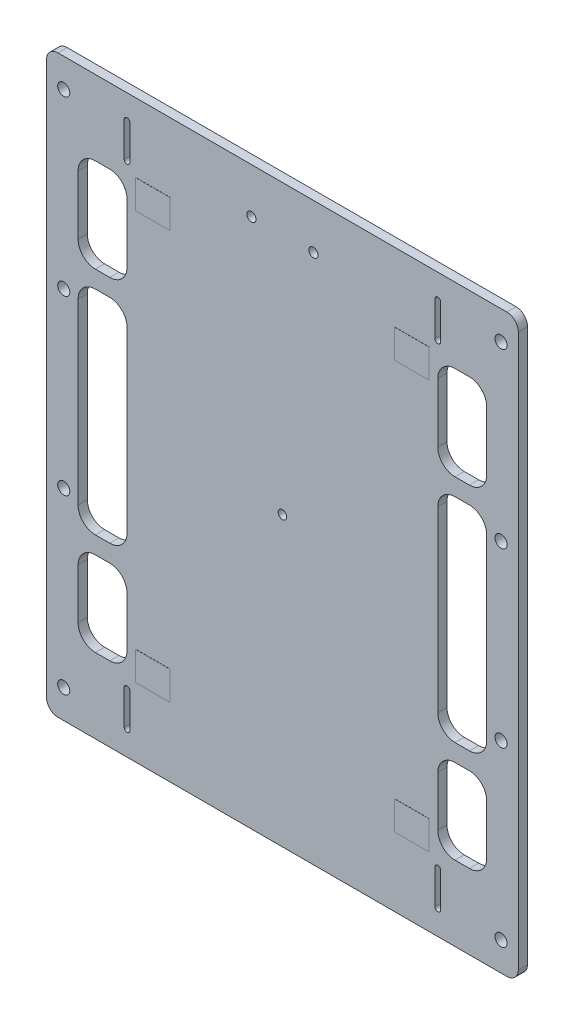
SolidWorks part; units mm, degrees
material "Oshpark board"
ref_plane "Front Plane" through (0, 0, 0) normal (0, 0, 1) x (1, 0, 0)
ref_plane "Top Plane" through (0, 0, 0) normal (0, 1, 0) x (1, 0, 0)
ref_plane "Right Plane" through (0, 0, 0) normal (1, 0, 0) x (0, 0, -1)
sketch "Sketch1" plane through (0, 0, 0) normal (0, 0, 1) x (1, 0, 0)
  line L1 (-39, -50) -> (39, -50)
  line L2 (-41, -48) -> (-41, 48)
  line L3 (-39, 50) -> (39, 50)
  line L4 (41, -48) -> (41, 48)
  line L5 (-41, -50) -> (41, 50) construction
  line L6 (-41, 50) -> (41, -50) construction
  arc A0 (-39, -50) -> (-41, -48) centre (-39, -48) cw
  arc A1 (39, -50) -> (41, -48) centre (39, -48) ccw
  arc A2 (39, 50) -> (41, 48) centre (39, 48) cw
  arc A3 (-41, 48) -> (-39, 50) centre (-39, 48) cw
  point P0 (0, 0)
  dimension "D3" = 2
  dimension "D1" = 100
  dimension "D2" = 82
extrude "boardOutline" add sketch "Sketch1" along normal blind 1.6
sketch "Sketch2" plane through (0, 0, 1.6) normal (0, 0, 1) x (1, 0, 0)
  line L0 (39, 50) -> (-39, 50) construction
  line L1 (-41, 48) -> (-41, -48) construction
  line L3 (-37.5, 44.2) -> (-37.5, 4.2) construction
  circle A0 centre (0, 0) radius 0.75
  circle A1 centre (-37.5, 44.2) radius 1.05 construction
  circle A2 centre (37.5, 44.2) radius 1.05 construction
  circle A3 centre (37.5, 4.2) radius 1.05 construction
  circle A4 centre (37.5, -35.8) radius 1.05 construction
  circle A5 centre (-37.5, 4.2) radius 1.05 construction
  circle A6 centre (-37.5, -35.8) radius 1.05 construction
  circle A7 centre (-5.38, 42.15) radius 0.8
  circle A8 centre (5.39, 42.15) radius 0.8
  dimension "D1" = 1.5
  dimension "D2" = 2.1
  dimension "D9" = 10.77
  dimension "D7" = 1.6
  dimension "D11" = 7.85
  dimension "D12" = 35.62
  dimension "D3" = 5.8
  dimension "D4" = 3.5
  dimension "D8" = 40
  dimension "D10" = 37.5
  dimension "D5" = 2
  dimension "D6" = 3
extrude "componentHoles" cut sketch "Sketch2" against normal through all
sketch "Sketch4" plane through (0, 0, 1.6) normal (0, 0, 1) x (1, 0, 0)
  line L0 (-27, 39.75) -> (-27, 45.75) construction
  line L1 (-27.5, 39.75) -> (-27.5, 45.75)
  line L2 (-26.5, 39.75) -> (-26.5, 45.75)
  line L3 (39, 50) -> (-39, 50) construction
  line L4 (-41, 48) -> (-41, -48) construction
  line L5 (27, 39.75) -> (27, 45.75) construction
  line L6 (26.5, 39.75) -> (26.5, 45.75)
  line L7 (27.5, 39.75) -> (27.5, 45.75)
  line L8 (27, -45.75) -> (27, -39.75) construction
  line L9 (26.5, -45.75) -> (26.5, -39.75)
  line L10 (27.5, -45.75) -> (27.5, -39.75)
  line L11 (-27, -45.75) -> (-27, -39.75) construction
  line L12 (-27.5, -45.75) -> (-27.5, -39.75)
  line L13 (-26.5, -45.75) -> (-26.5, -39.75)
  line L14 (-27, 39.75) -> (27, 39.75) construction
  line L15 (-39, -50) -> (39, -50) construction
  arc A0 (-27.5, 39.75) -> (-26.5, 39.75) centre (-27, 39.75) ccw
  arc A1 (-26.5, 45.75) -> (-27.5, 45.75) centre (-27, 45.75) ccw
  arc A2 (26.5, 39.75) -> (27.5, 39.75) centre (27, 39.75) ccw
  arc A3 (27.5, 45.75) -> (26.5, 45.75) centre (27, 45.75) ccw
  arc A4 (26.5, -45.75) -> (27.5, -45.75) centre (27, -45.75) ccw
  arc A5 (27.5, -39.75) -> (26.5, -39.75) centre (27, -39.75) ccw
  arc A6 (-27.5, -45.75) -> (-26.5, -45.75) centre (-27, -45.75) ccw
  arc A7 (-26.5, -39.75) -> (-27.5, -39.75) centre (-27, -39.75) ccw
  point P2 (-27, 42.75)
  point P16 (27, 42.75)
  point P23 (27, -42.75)
  point P30 (-27, -42.75)
  dimension "D1" = 4.25
  dimension "D2" = 13.5
  dimension "D3" = 1
  dimension "D4" = 6
  dimension "D7" = 54
  dimension "D8" = 14
  dimension "D9" = 4.25
  dimension "D10" = 4.25
  dimension "D5" = 2
  dimension "D6" = 2
extrude "solarCellContactHoles" cut sketch "Sketch4" against normal blind 1.6
sketch "Sketch3" plane through (0, 0, 1.6) normal (0, 0, 1) x (1, 0, 0)
  line L1 (-32.5, 37) -> (-30, 37)
  line L2 (-35.5, 34) -> (-35.5, 23.7)
  line L3 (-32.5, 20.7) -> (-30, 20.7)
  line L4 (-27, 34) -> (-27, 23.7)
  line L5 (-41, 48) -> (-41, -48) construction
  line L6 (-30, -22.3) -> (-32.5, -22.3)
  line L9 (0, 50) -> (0, -50) construction
  line L10 (39, 50) -> (-39, 50) construction
  line L11 (-39, -50) -> (39, -50) construction
  line L12 (-27, -25.3) -> (-27, -34)
  line L13 (-30, -37) -> (-32.5, -37)
  line L14 (-35.5, -25.3) -> (-35.5, -34)
  line L19 (-30, -19.3) -> (-32.5, -19.3)
  line L25 (-27, -16.3) -> (-27, 14.7)
  line L26 (-30, 17.7) -> (-32.5, 17.7)
  line L27 (-35.5, -16.3) -> (-35.5, 14.7)
  arc A0 (-35.5, 23.7) -> (-32.5, 20.7) centre (-32.5, 23.7) ccw
  arc A1 (-30, 20.7) -> (-27, 23.7) centre (-30, 23.7) ccw
  arc A2 (-30, 37) -> (-27, 34) centre (-30, 34) cw
  arc A3 (-32.5, 37) -> (-35.5, 34) centre (-32.5, 34) ccw
  arc A4 (-30, -19.3) -> (-27, -16.3) centre (-30, -16.3) ccw
  arc A5 (-27, -34) -> (-30, -37) centre (-30, -34) cw
  arc A6 (-32.5, -37) -> (-35.5, -34) centre (-32.5, -34) cw
  arc A7 (-32.5, -22.3) -> (-35.5, -25.3) centre (-32.5, -25.3) ccw
  arc A8 (-30, -22.3) -> (-27, -25.3) centre (-30, -25.3) cw
  arc A17 (-32.5, -19.3) -> (-35.5, -16.3) centre (-32.5, -16.3) cw
  arc A18 (-32.5, 17.7) -> (-35.5, 14.7) centre (-32.5, 14.7) ccw
  arc A19 (-27, 14.7) -> (-30, 17.7) centre (-30, 14.7) ccw
  point P12 (-27, 20.7)
  point P15 (-27, 37)
  point P18 (-35.5, 37)
  dimension "D5" = 3
  dimension "D10" = 13
  dimension "D7" = 3
  dimension "D11" = 3
  dimension "D1" = 8.5
  dimension "D2" = 29.3
  dimension "D3" = 13
  dimension "D4" = 5.5
  dimension "D8" = 3
  dimension "D9" = 3
  dimension "D6" = 37
extrude "windows_1side" cut sketch "Sketch3" against normal through all
sketch "Sketch5" plane through (0, 0, 1.6) normal (0, 0, 1) x (1, 0, 0)
  line L0 (-41, 48) -> (-41, -48) construction
  line L1 (-25.5, 38) -> (-19.5, 38)
  line L2 (-25.5, 38) -> (-25.5, 33)
  line L3 (-25.5, 33) -> (-19.5, 33)
  line L4 (-19.5, 38) -> (-19.5, 33)
  line L5 (39, 50) -> (-39, 50) construction
  line L6 (19.5, 38) -> (19.5, 33)
  line L7 (25.5, 38) -> (25.5, 33)
  line L8 (19.5, 33) -> (25.5, 33)
  line L9 (19.5, 38) -> (25.5, 38)
  line L10 (19.5, -33) -> (19.5, -38)
  line L11 (25.5, -33) -> (25.5, -38)
  line L12 (19.5, -38) -> (25.5, -38)
  line L13 (19.5, -33) -> (25.5, -33)
  line L14 (-25.5, -33) -> (-25.5, -38)
  line L15 (-19.5, -33) -> (-19.5, -38)
  line L16 (-25.5, -38) -> (-19.5, -38)
  line L17 (-25.5, -33) -> (-19.5, -33)
  line L18 (-25.5, 38) -> (19.5, 38) construction
  line L19 (-25.5, 38) -> (-25.5, -33) construction
  dimension "D1" = 5
  dimension "D2" = 6
  dimension "D3" = 15.5
  dimension "D4" = 12
  dimension "D7" = 45
  dimension "D8" = 71
  dimension "D5" = 2
  dimension "D6" = 2
extrude "contactPads" add sketch "Sketch5" along normal blind 0.02
hole_wizard "M2 Clearance Hole1" positions "Sketch6" profile "Sketch7" hole size "M2" standard "ANSI Metric" end condition through all
sketch "Sketch6" plane through (0, 0, 0) normal (0, 0, -1) x (-1, 0, 0)
  line L5 (38, -50) -> (38, -45) construction
  line L6 (39, -50) -> (-39, -50) construction
  line L7 (38, -45) -> (38, -15) construction
  line L8 (38, -15) -> (38, 15) construction
  line L9 (38, 15) -> (38, 45) construction
  line L10 (38, 45) -> (38, 50) construction
  line L11 (-39, 50) -> (39, 50) construction
  line L14 (41, 48) -> (41, -48) construction
  point P0 (38, 45)
  point P27 (38, -15)
  point P36 (38, -45)
  point P38 (38, 15)
  dimension "D1" = 3
  dimension "D2" = 5
sketch "Sketch7" plane through (-38, 45, 0) normal (1, 0, 0) x (0, 1, 0)
  line L0 (0, 0) -> (0, 1.62)
  line L1 (0, 1.62) -> (1.05, 1.62)
  line L2 (1.05, 1.62) -> (1.05, 0)
  line L5 (1.05, 0) -> (0, 0)
  line L11 (0, -6.35) -> (0, 107.95) construction
  dimension "Thru Hole Dia." = 2.1
  dimension "Thru Hole Depth" = 1.62
mirror "Mirror1" about plane through (0, 0, 0) normal (1, 0, 0) of "M2 Clearance Hole1", "windows_1side"
sketch "Sketch8" [suppressed] plane through (0, 0, 1.6) normal (0, 0, 1) x (1, 0, 0)
  line L0 (-15, -16.3) -> (-15, 14.7)
  line L1 (-15, -16.3) -> (-15, 14.7)
  line L2 (12, -19.3) -> (-12, -19.3)
  line L3 (12, -19.3) -> (-12, -19.3)
  line L4 (15, 14.7) -> (15, -16.3)
  line L5 (15, 14.7) -> (15, -16.3)
  line L6 (-12, 17.7) -> (12, 17.7)
  line L7 (-12, 17.7) -> (12, 17.7)
  line L8 (-32.5, 17.7) -> (-21, 17.7)
  line L9 (-32.5, 17.7) -> (-21, 17.7)
  line L10 (-35.5, 14.7) -> (-35.5, -16.3)
  line L11 (-35.5, 14.7) -> (-35.5, -16.3)
  line L12 (-21, -19.3) -> (-32.5, -19.3)
  line L13 (-21, -19.3) -> (-32.5, -19.3)
  line L14 (-18, 14.7) -> (-18, -16.3)
  line L15 (-18, 14.7) -> (-18, -16.3)
  line L16 (18, -16.3) -> (18, 14.7)
  line L17 (18, -16.3) -> (18, 14.7)
  line L18 (32.5, -19.3) -> (21, -19.3)
  line L19 (32.5, -19.3) -> (21, -19.3)
  line L20 (35.5, -16.3) -> (35.5, 14.7)
  line L21 (35.5, -16.3) -> (35.5, 14.7)
  line L22 (21, 17.7) -> (32.5, 17.7)
  line L23 (21, 17.7) -> (32.5, 17.7)
  line L24 (-15, -44) -> (-15, -25.3)
  line L25 (-15, -44) -> (-15, -25.3)
  line L26 (12, -47) -> (-12, -47)
  line L27 (12, -47) -> (-12, -47)
  line L28 (15, -25.3) -> (15, -44)
  line L29 (15, -25.3) -> (15, -44)
  line L30 (-12, -22.3) -> (12, -22.3)
  line L31 (-12, -22.3) -> (12, -22.3)
  line L32 (-35.5, -25.3) -> (-35.5, -44)
  line L33 (-35.5, -25.3) -> (-35.5, -44)
  line L34 (-32.5, -22.3) -> (-21, -22.3)
  line L35 (-32.5, -22.3) -> (-21, -22.3)
  line L36 (-18, -25.3) -> (-18, -44)
  line L37 (-18, -25.3) -> (-18, -44)
  line L38 (-21, -47) -> (-32.5, -47)
  line L39 (-21, -47) -> (-32.5, -47)
  line L40 (18, -44) -> (18, -25.3)
  line L41 (18, -44) -> (18, -25.3)
  line L42 (32.5, -47) -> (21, -47)
  line L43 (32.5, -47) -> (21, -47)
  line L44 (35.5, -44) -> (35.5, -25.3)
  line L45 (35.5, -44) -> (35.5, -25.3)
  line L46 (21, -22.3) -> (32.5, -22.3)
  line L47 (21, -22.3) -> (32.5, -22.3)
  line L48 (-15, 23.7) -> (-15, 43.5)
  line L49 (-15, 23.7) -> (-15, 43.5)
  line L50 (12, 20.7) -> (-12, 20.7)
  line L51 (12, 20.7) -> (-12, 20.7)
  line L52 (15, 43.5) -> (15, 23.7)
  line L53 (15, 43.5) -> (15, 23.7)
  line L54 (12, 46.5) -> (-12, 46.5)
  line L55 (12, 46.5) -> (-12, 46.5)
  line L56 (-35.5, 43.5) -> (-35.5, 23.7)
  line L57 (-35.5, 43.5) -> (-35.5, 23.7)
  line L58 (-21, 20.7) -> (-32.5, 20.7)
  line L59 (-21, 20.7) -> (-32.5, 20.7)
  line L60 (-18, 43.5) -> (-18, 23.7)
  line L61 (-18, 43.5) -> (-18, 23.7)
  line L62 (-21, 46.5) -> (-32.5, 46.5)
  line L63 (-21, 46.5) -> (-32.5, 46.5)
  line L64 (18, 23.7) -> (18, 43.5)
  line L65 (18, 23.7) -> (18, 43.5)
  line L66 (32.5, 20.7) -> (21, 20.7)
  line L67 (32.5, 20.7) -> (21, 20.7)
  line L68 (35.5, 23.7) -> (35.5, 43.5)
  line L69 (35.5, 23.7) -> (35.5, 43.5)
  line L70 (32.5, 46.5) -> (21, 46.5)
  line L71 (32.5, 46.5) -> (21, 46.5)
  line L72 (-32.5, -50) -> (-21, -50)
  line L73 (-32.5, -50) -> (-21, -50)
  line L74 (-12, -50) -> (12, -50)
  line L75 (-12, -50) -> (12, -50)
  line L76 (21, -50) -> (32.5, -50)
  line L77 (21, -50) -> (32.5, -50)
  line L78 (-39, -50) -> (39, -50) construction
  line L79 (41, -48) -> (41, 48) construction
  line L80 (39, 50) -> (-39, 50) construction
  line L81 (-41, 48) -> (-41, -48) construction
  line L82 (-39, -50) -> (39, -50)
  line L83 (41, -48) -> (41, 48)
  line L84 (39, 50) -> (-39, 50)
  line L85 (-41, 48) -> (-41, -48)
  line L86 (-35.5, 43.5) -> (-35.5, 23.7)
  line L87 (35.5, -157.5) -> (35.5, -137.7)
  line L88 (-35.5, -25.3) -> (-35.5, -44)
  line L89 (-35.5, -53) -> (-35.5, -61)
  line L90 (-35.5, -70) -> (-35.5, -88.7)
  line L91 (-35.5, -97.7) -> (-35.5, -128.7)
  line L92 (-35.5, -137.7) -> (-35.5, -157.5)
  line L93 (-35.5, -137.7) -> (-35.5, -157.5)
  line L94 (-35.5, -97.7) -> (-35.5, -128.7)
  line L95 (-35.5, -70) -> (-35.5, -88.7)
  line L96 (-35.5, -53) -> (-35.5, -61)
  line L97 (-35.5, -25.3) -> (-35.5, -44)
  line L98 (-35.5, 43.5) -> (-35.5, 23.7)
  line L99 (35.5, -128.7) -> (35.5, -97.7)
  line L100 (35.5, -88.7) -> (35.5, -70)
  line L101 (35.5, -61) -> (35.5, -53)
  line L102 (35.5, -44) -> (35.5, -25.3)
  line L103 (-35.5, 43.5) -> (-35.5, 23.7)
  line L104 (35.5, 23.7) -> (35.5, 43.5)
  line L105 (35.5, 23.7) -> (35.5, 43.5)
  line L106 (35.5, -44) -> (35.5, -25.3)
  line L107 (35.5, -61) -> (35.5, -53)
  line L108 (35.5, -88.7) -> (35.5, -70)
  line L109 (35.5, -128.7) -> (35.5, -97.7)
  line L110 (35.5, -157.5) -> (35.5, -137.7)
  line L111 (-35.5, 14.7) -> (-35.5, -16.3)
  line L112 (35.5, -157.5) -> (35.5, -137.7)
  line L113 (-35.5, -53) -> (-35.5, -61)
  line L114 (-35.5, -70) -> (-35.5, -88.7)
  line L115 (-35.5, -97.7) -> (-35.5, -128.7)
  line L116 (-35.5, -137.7) -> (-35.5, -157.5)
  line L117 (-35.5, -137.7) -> (-35.5, -157.5)
  line L118 (-35.5, -97.7) -> (-35.5, -128.7)
  line L119 (-35.5, -70) -> (-35.5, -88.7)
  line L120 (-35.5, -53) -> (-35.5, -61)
  line L121 (-35.5, 14.7) -> (-35.5, -16.3)
  line L122 (-35.5, 43.5) -> (-35.5, 23.7)
  line L123 (35.5, -128.7) -> (35.5, -97.7)
  line L124 (35.5, -88.7) -> (35.5, -70)
  line L125 (35.5, -61) -> (35.5, -53)
  line L126 (35.5, -157.5) -> (35.5, -137.7)
  line L127 (35.5, -16.3) -> (35.5, 14.7)
  line L128 (35.5, 23.7) -> (35.5, 43.5)
  line L129 (35.5, 23.7) -> (35.5, 43.5)
  line L130 (35.5, -16.3) -> (35.5, 14.7)
  line L131 (35.5, -61) -> (35.5, -53)
  line L132 (35.5, -88.7) -> (35.5, -70)
  line L133 (35.5, -128.7) -> (35.5, -97.7)
  line L134 (35.5, -157.5) -> (35.5, -137.7)
  line L135 (-35.5, 14.7) -> (-35.5, -16.3)
  line L136 (-35.5, -25.3) -> (-35.5, -44)
  line L137 (-35.5, -53) -> (-35.5, -61)
  line L138 (-35.5, -70) -> (-35.5, -88.7)
  line L139 (-35.5, -97.7) -> (-35.5, -128.7)
  line L140 (-35.5, -137.7) -> (-35.5, -157.5)
  line L141 (-35.5, -137.7) -> (-35.5, -157.5)
  line L142 (-35.5, -97.7) -> (-35.5, -128.7)
  line L143 (-35.5, -70) -> (-35.5, -88.7)
  line L144 (-35.5, -53) -> (-35.5, -61)
  line L145 (-35.5, -25.3) -> (-35.5, -44)
  line L146 (-35.5, 14.7) -> (-35.5, -16.3)
  line L147 (35.5, -128.7) -> (35.5, -97.7)
  line L148 (35.5, -88.7) -> (35.5, -70)
  line L149 (35.5, -61) -> (35.5, -53)
  line L150 (35.5, -44) -> (35.5, -25.3)
  line L151 (35.5, -16.3) -> (35.5, 14.7)
  line L153 (35.5, -16.3) -> (35.5, 14.7)
  line L154 (35.5, -44) -> (35.5, -25.3)
  line L155 (35.5, -61) -> (35.5, -53)
  line L156 (35.5, -88.7) -> (35.5, -70)
  line L157 (35.5, -128.7) -> (35.5, -97.7)
  line L158 (35.5, -157.5) -> (35.5, -137.7)
  arc A0 (-15, -16.3) -> (-12, -19.3) centre (-12, -16.3) ccw
  arc A1 (-15, -16.3) -> (-12, -19.3) centre (-12, -16.3) ccw
  arc A2 (12, -19.3) -> (15, -16.3) centre (12, -16.3) ccw
  arc A3 (12, -19.3) -> (15, -16.3) centre (12, -16.3) ccw
  arc A4 (15, 14.7) -> (12, 17.7) centre (12, 14.7) ccw
  arc A5 (15, 14.7) -> (12, 17.7) centre (12, 14.7) ccw
  arc A6 (-12, 17.7) -> (-15, 14.7) centre (-12, 14.7) ccw
  arc A7 (-12, 17.7) -> (-15, 14.7) centre (-12, 14.7) ccw
  arc A8 (-18, 14.7) -> (-21, 17.7) centre (-21, 14.7) ccw
  arc A9 (-18, 14.7) -> (-21, 17.7) centre (-21, 14.7) ccw
  arc A10 (-32.5, 17.7) -> (-35.5, 14.7) centre (-32.5, 14.7) ccw
  arc A11 (-32.5, 17.7) -> (-35.5, 14.7) centre (-32.5, 14.7) ccw
  arc A12 (-35.5, -16.3) -> (-32.5, -19.3) centre (-32.5, -16.3) ccw
  arc A13 (-35.5, -16.3) -> (-32.5, -19.3) centre (-32.5, -16.3) ccw
  arc A14 (-21, -19.3) -> (-18, -16.3) centre (-21, -16.3) ccw
  arc A15 (-21, -19.3) -> (-18, -16.3) centre (-21, -16.3) ccw
  arc A16 (18, -16.3) -> (21, -19.3) centre (21, -16.3) ccw
  arc A17 (18, -16.3) -> (21, -19.3) centre (21, -16.3) ccw
  arc A18 (32.5, -19.3) -> (35.5, -16.3) centre (32.5, -16.3) ccw
  arc A19 (32.5, -19.3) -> (35.5, -16.3) centre (32.5, -16.3) ccw
  arc A20 (35.5, 14.7) -> (32.5, 17.7) centre (32.5, 14.7) ccw
  arc A21 (35.5, 14.7) -> (32.5, 17.7) centre (32.5, 14.7) ccw
  arc A22 (21, 17.7) -> (18, 14.7) centre (21, 14.7) ccw
  arc A23 (21, 17.7) -> (18, 14.7) centre (21, 14.7) ccw
  arc A24 (-15, -44) -> (-12, -47) centre (-12, -44) ccw
  arc A25 (-15, -44) -> (-12, -47) centre (-12, -44) ccw
  arc A26 (12, -47) -> (15, -44) centre (12, -44) ccw
  arc A27 (12, -47) -> (15, -44) centre (12, -44) ccw
  arc A28 (15, -25.3) -> (12, -22.3) centre (12, -25.3) ccw
  arc A29 (15, -25.3) -> (12, -22.3) centre (12, -25.3) ccw
  arc A30 (-12, -22.3) -> (-15, -25.3) centre (-12, -25.3) ccw
  arc A31 (-12, -22.3) -> (-15, -25.3) centre (-12, -25.3) ccw
  arc A32 (-32.5, -22.3) -> (-35.5, -25.3) centre (-32.5, -25.3) ccw
  arc A33 (-32.5, -22.3) -> (-35.5, -25.3) centre (-32.5, -25.3) ccw
  arc A34 (-18, -25.3) -> (-21, -22.3) centre (-21, -25.3) ccw
  arc A35 (-18, -25.3) -> (-21, -22.3) centre (-21, -25.3) ccw
  arc A36 (-21, -47) -> (-18, -44) centre (-21, -44) ccw
  arc A37 (-21, -47) -> (-18, -44) centre (-21, -44) ccw
  arc A38 (-35.5, -44) -> (-32.5, -47) centre (-32.5, -44) ccw
  arc A39 (-35.5, -44) -> (-32.5, -47) centre (-32.5, -44) ccw
  arc A40 (18, -44) -> (21, -47) centre (21, -44) ccw
  arc A41 (18, -44) -> (21, -47) centre (21, -44) ccw
  arc A42 (32.5, -47) -> (35.5, -44) centre (32.5, -44) ccw
  arc A43 (32.5, -47) -> (35.5, -44) centre (32.5, -44) ccw
  arc A44 (35.5, -25.3) -> (32.5, -22.3) centre (32.5, -25.3) ccw
  arc A45 (35.5, -25.3) -> (32.5, -22.3) centre (32.5, -25.3) ccw
  arc A46 (21, -22.3) -> (18, -25.3) centre (21, -25.3) ccw
  arc A47 (21, -22.3) -> (18, -25.3) centre (21, -25.3) ccw
  arc A48 (-15, 23.7) -> (-12, 20.7) centre (-12, 23.7) ccw
  arc A49 (-15, 23.7) -> (-12, 20.7) centre (-12, 23.7) ccw
  arc A50 (12, 20.7) -> (15, 23.7) centre (12, 23.7) ccw
  arc A51 (12, 20.7) -> (15, 23.7) centre (12, 23.7) ccw
  arc A52 (15, 43.5) -> (12, 46.5) centre (12, 43.5) ccw
  arc A53 (15, 43.5) -> (12, 46.5) centre (12, 43.5) ccw
  arc A54 (-12, 46.5) -> (-15, 43.5) centre (-12, 43.5) ccw
  arc A55 (-12, 46.5) -> (-15, 43.5) centre (-12, 43.5) ccw
  arc A56 (-35.5, 23.7) -> (-32.5, 20.7) centre (-32.5, 23.7) ccw
  arc A57 (-35.5, 23.7) -> (-32.5, 20.7) centre (-32.5, 23.7) ccw
  arc A58 (-21, 20.7) -> (-18, 23.7) centre (-21, 23.7) ccw
  arc A59 (-21, 20.7) -> (-18, 23.7) centre (-21, 23.7) ccw
  arc A60 (-18, 43.5) -> (-21, 46.5) centre (-21, 43.5) ccw
  arc A61 (-18, 43.5) -> (-21, 46.5) centre (-21, 43.5) ccw
  arc A62 (-32.5, 46.5) -> (-35.5, 43.5) centre (-32.5, 43.5) ccw
  arc A63 (-32.5, 46.5) -> (-35.5, 43.5) centre (-32.5, 43.5) ccw
  arc A64 (18, 23.7) -> (21, 20.7) centre (21, 23.7) ccw
  arc A65 (18, 23.7) -> (21, 20.7) centre (21, 23.7) ccw
  arc A66 (32.5, 20.7) -> (35.5, 23.7) centre (32.5, 23.7) ccw
  arc A67 (32.5, 20.7) -> (35.5, 23.7) centre (32.5, 23.7) ccw
  arc A68 (35.5, 43.5) -> (32.5, 46.5) centre (32.5, 43.5) ccw
  arc A69 (35.5, 43.5) -> (32.5, 46.5) centre (32.5, 43.5) ccw
  arc A70 (21, 46.5) -> (18, 43.5) centre (21, 43.5) ccw
  arc A71 (21, 46.5) -> (18, 43.5) centre (21, 43.5) ccw
  arc A72 (-32.5, -50) -> (-35.5, -53) centre (-32.5, -53) ccw
  arc A73 (-32.5, -50) -> (-34.7361, -50) centre (-32.5, -53) ccw
  arc A74 (-18, -53) -> (-21, -50) centre (-21, -53) ccw
  arc A75 (-18.7639, -50) -> (-21, -50) centre (-21, -53) ccw
  arc A76 (-12, -50) -> (-15, -53) centre (-12, -53) ccw
  arc A77 (-12, -50) -> (-14.2361, -50) centre (-12, -53) ccw
  arc A78 (15, -53) -> (12, -50) centre (12, -53) ccw
  arc A79 (14.2361, -50) -> (12, -50) centre (12, -53) ccw
  arc A80 (21, -50) -> (18, -53) centre (21, -53) ccw
  arc A81 (21, -50) -> (18.7639, -50) centre (21, -53) ccw
  arc A82 (35.5, -53) -> (32.5, -50) centre (32.5, -53) ccw
  arc A83 (34.7361, -50) -> (32.5, -50) centre (32.5, -53) ccw
  arc A84 (-41, -48) -> (-39, -50) centre (-39, -48) ccw construction
  arc A85 (39, -50) -> (41, -48) centre (39, -48) ccw construction
  arc A86 (41, 48) -> (39, 50) centre (39, 48) ccw construction
  arc A87 (-39, 50) -> (-41, 48) centre (-39, 48) ccw construction
  arc A88 (-41, -48) -> (-39, -50) centre (-39, -48) ccw
  arc A89 (39, -50) -> (41, -48) centre (39, -48) ccw
  arc A90 (41, 48) -> (39, 50) centre (39, 48) ccw
  arc A91 (-39, 50) -> (-41, 48) centre (-39, 48) ccw
